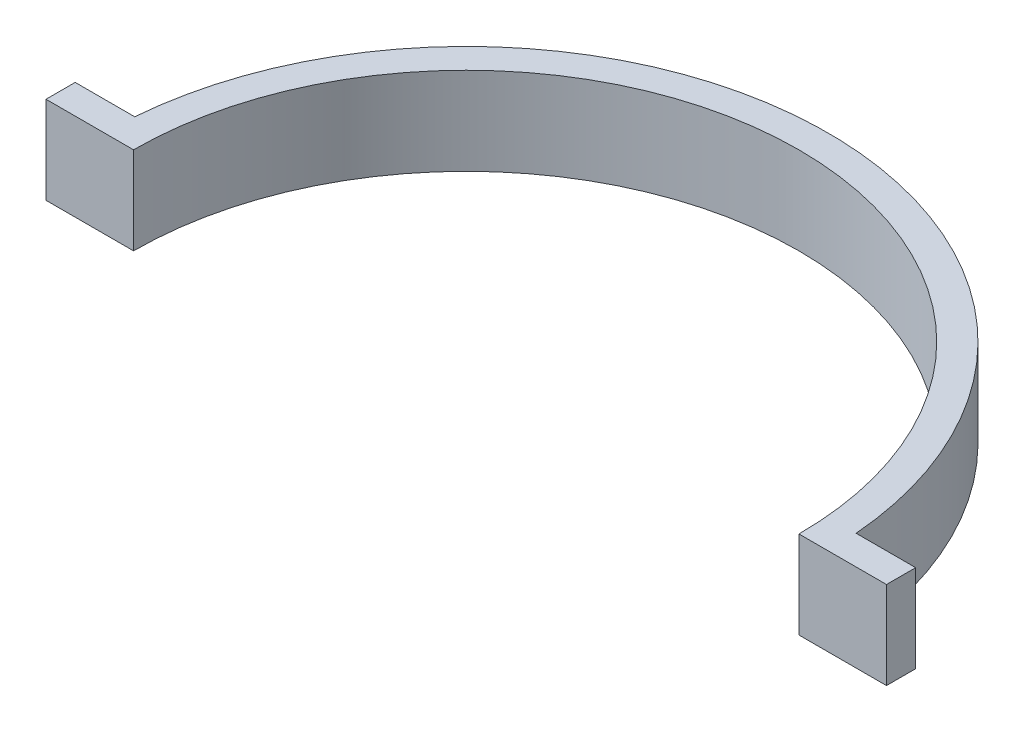
SolidWorks part; units mm, degrees
ref_plane "Front Plane" through (0, 0, 0) normal (0, 0, 1) x (1, 0, 0)
ref_plane "Top Plane" through (0, 0, 0) normal (0, 1, 0) x (1, 0, 0)
ref_plane "Right Plane" through (0, 0, 0) normal (1, 0, 0) x (0, 0, -1)
sketch "Sketch1" plane through (0, 0, 0) normal (0, 0, 1) x (1, 0, 0)
  line L0 (0, -72.1064) -> (0, 64.4543) construction
  line L1 (0, 0) -> (113.31, 0) construction
  line L3 (36.195, -4.7625) -> (39.37, -4.7625)
  line L4 (36.195, -4.7625) -> (36.195, 4.7625)
  line L5 (36.195, 4.7625) -> (39.37, 4.7625)
  line L6 (39.37, -4.7625) -> (39.37, 4.7625)
  line L7 (36.195, -4.7625) -> (39.37, 4.7625) construction
  line L8 (36.195, 4.7625) -> (39.37, -4.7625) construction
  point P5 (37.7825, 0)
  dimension "D1" = 36.195
  dimension "D2" = 3.175
  dimension "D3" = 9.525
revolve "Revolve1" add sketch "Sketch1" angle 180 about L0
ref_plane "Plane1" through (39.37, 0, 0) normal (1, 0, 0) x (0, 0, -1)
sketch "Sketch2" plane through (39.37, 0, 0) normal (1, 0, 0) x (0, 0, -1)
  line L0 (0, 4.7625) -> (0, -4.7625)
  line L1 (0, 4.7625) -> (3.175, 4.7625)
  line L2 (0, -4.7625) -> (3.175, -4.7625)
  line L3 (3.175, 4.7625) -> (3.175, -4.7625)
  dimension "D1" = 3.175
extrude "Boss-Extrude1" add sketch "Sketch2" against normal up to surface up to face at (0, 0, -19.685)
extrude "Boss-Extrude2" add sketch "Sketch2<2>" along normal blind 6.35
sketch "Sketch2<2>" plane through (39.37, 0, 0) normal (1, 0, 0) x (0, 0, -1) same geometry as "Sketch2"
ref_plane "Plane2" through (-39.37, 0, 0) normal (-1, 0, 0) x (0, 0, 1)
sketch "Sketch4" plane through (-39.37, 0, 0) normal (-1, 0, 0) x (0, 0, 1)
  line L0 (0, 4.7625) -> (0, -4.7625)
  line L1 (0, 4.7625) -> (-3.175, 4.7625)
  line L2 (0, -4.7625) -> (-3.175, -4.7625)
  line L3 (-3.175, 4.7625) -> (-3.175, -4.7625)
  dimension "D1" = 3.175
extrude "Boss-Extrude3" add sketch "Sketch4" against normal up to surface up to face at (-0.8265, 0, -20.4627)
extrude "Boss-Extrude4" add sketch "Sketch4<2>" along normal blind 6.35
sketch "Sketch4<2>" plane through (-39.37, 0, 0) normal (-1, 0, 0) x (0, 0, 1) same geometry as "Sketch4"
